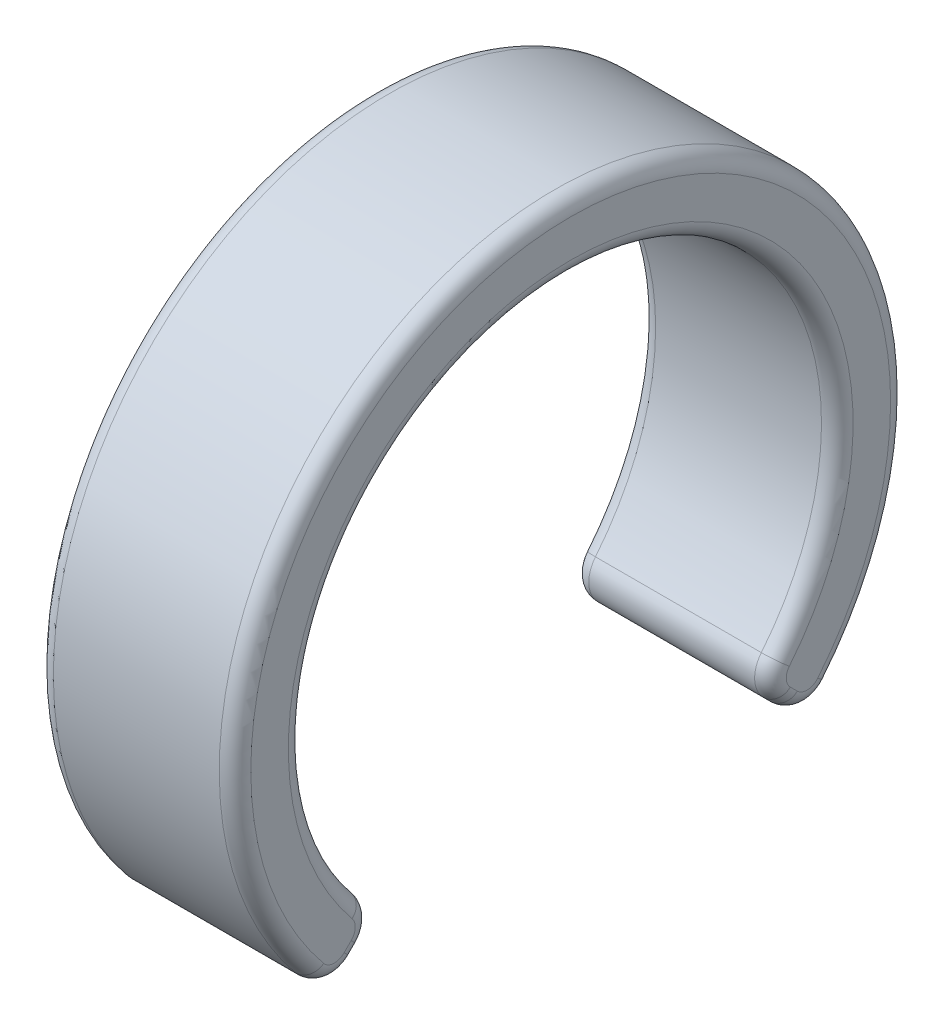
SolidWorks part; units mm, degrees
ref_plane "Ebene vorne" through (0, 0, 0) normal (0, 0, 1) x (1, 0, 0)
ref_plane "Ebene oben" through (0, 0, 0) normal (0, 1, 0) x (1, 0, 0)
ref_plane "Ebene rechts" through (0, 0, 0) normal (1, 0, 0) x (0, 0, -1)
ref_axis "Achse1" through (-5.5, 0, 0) along (1, 0, 0)
sketch "Skizze1" plane through (0, 0, 0) normal (0, 0, 1) x (1, 0, 0)
  line L0 (0, 49.3199) -> (0, -49.2034) construction
  line L1 (-29.2309, 0) -> (28.6486, 0) construction
  line L2 (-5.5, 0) -> (5.5, 0) construction
  line L3 (-5, 17) -> (5, 17)
  line L4 (5, 17) -> (5, 13.5)
  line L5 (5, 13.5) -> (-5, 13.5)
  line L6 (-5, 17) -> (-5, 13.5)
  point P12 (0, 13.5)
  point P13 (0, 17)
  dimension "D1" = 27
  dimension "D2" = 10
  dimension "D3" = 3.5
revolve "Rotation1" add sketch "Skizze1" angle 270 mid plane about L1
fillet "Verrundung1" radius 1.5 4 edges at (0, -12.0208, -12.0208) (0, -9.5459, -9.5459) (0, -9.5459, 9.5459) (0, -12.0208, 12.0208)
fillet "Verrundung2" radius 0.8 16 edges at (5, -11.3463, 12.042) (5, -10.7311, 10.7311) (5, -9.5679, 10.116) (5, 13.5, 0) (5, -9.5679, -10.116) (5, -10.7311, -10.7311) (5, -11.3463, -12.042) (-5, -9.5679, 10.116) (-5, -10.7311, 10.7311) (-5, -11.3463, 12.042) (-5, 17, 0) (-5, -11.3463, -12.042) (-5, -10.7311, -10.7311) (-5, -9.5679, -10.116) (5, 17, 0) (-5, 13.5, 0)
